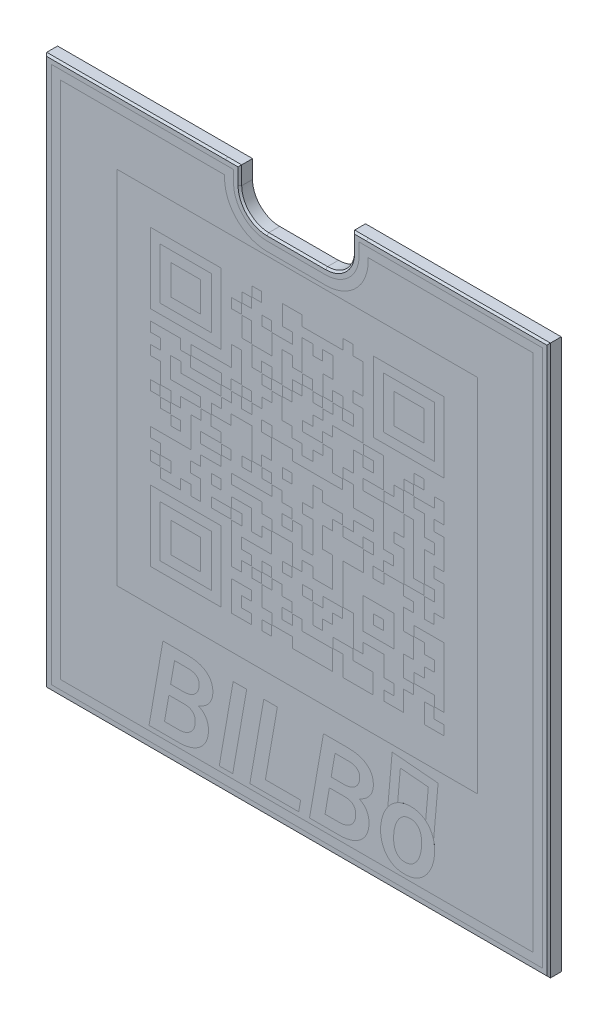
SolidWorks part; units mm, degrees
ref_plane "Front Plane" through (0, 0, 0) normal (0, 0, 1) x (1, 0, 0)
ref_plane "Top Plane" through (0, 0, 0) normal (0, 1, 0) x (1, 0, 0)
ref_plane "Right Plane" through (0, 0, 0) normal (1, 0, 0) x (0, 0, -1)
sketch "Sketch1" plane through (0, 0, 0) normal (0, 0, 1) x (1, 0, 0)
  line L0 (48, -68) -> (-48, -68) construction
  line L1 (56, -32.5) -> (56, -60) construction
  line L2 (56, 46) -> (56, -24.5) construction
  line L3 (-56, -24.5) -> (-56, 46) construction
  line L5 (-15, 54.4) -> (-15, 29) construction
  line L6 (-15, 29) -> (15, 29) construction
  line L7 (15, 29) -> (15, 54) construction
  line L8 (48, 54) -> (15, 54) construction
  line L9 (48, -68) -> (-48, -68) construction
  line L10 (56, -32.5) -> (56, -60) construction
  line L11 (56, 46) -> (56, -24.5) construction
  line L12 (-56, -24.5) -> (-56, 46) construction
  line L13 (-15, 54.4) -> (-48, 54.4) construction
  line L14 (-15, 54.4) -> (-15, 29) construction
  line L15 (-15, 29) -> (15, 29) construction
  line L16 (15, 29) -> (15, 54) construction
  line L17 (48, 54) -> (15, 54) construction
  line L18 (-15.25, 54.05) -> (-15.25, 28.75)
  line L19 (-55.65, 54.05) -> (-15.25, 54.05)
  line L20 (-55.65, 54.05) -> (-55.65, -67.65)
  line L21 (-55.65, -67.65) -> (55.825, -67.65)
  line L22 (55.825, 54.05) -> (55.825, -67.65)
  line L23 (-15.25, 28.75) -> (15.125, 28.75)
  line L24 (15.125, 28.75) -> (15.125, 54.05)
  line L25 (15.125, 54.05) -> (55.825, 54.05)
  circle A0 centre (-52, -64) radius 2.1 construction
  circle A3 centre (52, 50) radius 2.1 construction
  circle A4 centre (-52, 50) radius 2.1 construction
  circle A5 centre (-52, -64) radius 2.1 construction
  circle A6 centre (-52, 2.9) radius 2.15 construction
  circle A7 centre (52, 2.9) radius 2.15 construction
  circle A8 centre (52, 50) radius 2.1 construction
  circle A9 centre (-52, 50) radius 2.1 construction
  circle A10 centre (-52, 50) radius 1.35
  circle A11 centre (-52, 2.9) radius 1.35
  circle A12 centre (-52, -64) radius 1.35
  circle A13 centre (52, 50) radius 1.35
  circle A14 centre (52, 2.9) radius 1.35
  circle A15 centre (52, -64) radius 1.35
  circle A16 centre (-52, 2.9) radius 2.15 construction
  circle A17 centre (52, 2.9) radius 2.15 construction
  dimension "D5" = 2.7
  dimension "D1" = 0.35
  dimension "D2" = 0.35
  dimension "D3" = 0.35
  dimension "D4" = 0.35
  dimension "D6" = 0.25
  dimension "D7" = 0.25
  dimension "D8" = 0.25
extrude "Boss-Extrude1" add sketch "Sketch1" along normal blind 2.8
sketch "Sketch2" plane through (0, 0, 2.8) normal (0, 0, 1) x (1, 0, 0)
  line L5 (15.125, 28.75) -> (-15.25, 28.75) construction
  line L8 (-45.5, -63.25) -> (45.5, -63.25)
  line L9 (-45.5, -63.25) -> (-45.5, 27.75)
  line L10 (-45.5, 27.75) -> (45.5, 27.75)
  line L11 (45.5, -63.25) -> (45.5, 27.75)
  line L31 (-42, 24.25) -> (-28, 24.25)
  line L32 (-42, 24.25) -> (-42, 10.25)
  line L33 (-42, 10.25) -> (-28, 10.25)
  line L34 (-28, 24.25) -> (-28, 10.25)
  line L35 (-28, 24.25) -> (-14, 24.25)
  line L36 (-28, 24.25) -> (-28, 10.25)
  line L37 (-28, 10.25) -> (-14, 10.25)
  line L38 (-14, 24.25) -> (-14, 10.25)
  line L39 (-14, 24.25) -> (0, 24.25)
  line L40 (-14, 24.25) -> (-14, 10.25)
  line L41 (-14, 10.25) -> (0, 10.25)
  line L42 (0, 24.25) -> (0, 10.25)
  line L43 (0, 24.25) -> (14, 24.25)
  line L44 (0, 24.25) -> (0, 10.25)
  line L45 (0, 10.25) -> (14, 10.25)
  line L46 (14, 24.25) -> (14, 10.25)
  line L47 (14, 24.25) -> (28, 24.25)
  line L48 (14, 24.25) -> (14, 10.25)
  line L49 (14, 10.25) -> (28, 10.25)
  line L50 (28, 24.25) -> (28, 10.25)
  line L51 (28, 24.25) -> (42, 24.25)
  line L52 (28, 24.25) -> (28, 10.25)
  line L53 (28, 10.25) -> (42, 10.25)
  line L54 (42, 24.25) -> (42, 10.25)
  line L55 (-42, 10.25) -> (-28, 10.25)
  line L56 (-42, 10.25) -> (-42, -3.75)
  line L57 (-42, -3.75) -> (-28, -3.75)
  line L58 (-28, 10.25) -> (-28, -3.75)
  line L59 (-28, -3.75) -> (-14, -3.75)
  line L60 (-28, -3.75) -> (-28, 10.25)
  line L61 (-28, 10.25) -> (-14, 10.25)
  line L62 (-14, -3.75) -> (-14, 10.25)
  line L63 (-14, -3.75) -> (0, -3.75)
  line L64 (-14, -3.75) -> (-14, 10.25)
  line L65 (-14, 10.25) -> (0, 10.25)
  line L66 (0, -3.75) -> (0, 10.25)
  line L67 (0, -3.75) -> (14, -3.75)
  line L68 (0, -3.75) -> (0, 10.25)
  line L69 (0, 10.25) -> (14, 10.25)
  line L70 (14, -3.75) -> (14, 10.25)
  line L71 (14, -3.75) -> (28, -3.75)
  line L72 (14, -3.75) -> (14, 10.25)
  line L73 (14, 10.25) -> (28, 10.25)
  line L74 (28, -3.75) -> (28, 10.25)
  line L75 (28, -3.75) -> (42, -3.75)
  line L76 (28, -3.75) -> (28, 10.25)
  line L77 (28, 10.25) -> (42, 10.25)
  line L78 (42, -3.75) -> (42, 10.25)
  line L79 (42, -3.75) -> (28, -3.75)
  line L80 (42, -3.75) -> (42, -17.75)
  line L81 (42, -17.75) -> (28, -17.75)
  line L82 (28, -3.75) -> (28, -17.75)
  line L83 (14, -3.75) -> (28, -3.75)
  line L84 (14, -3.75) -> (14, -17.75)
  line L85 (14, -17.75) -> (28, -17.75)
  line L86 (28, -3.75) -> (28, -17.75)
  line L87 (0, -3.75) -> (14, -3.75)
  line L88 (0, -3.75) -> (0, -17.75)
  line L89 (0, -17.75) -> (14, -17.75)
  line L90 (14, -3.75) -> (14, -17.75)
  line L91 (-14, -3.75) -> (0, -3.75)
  line L92 (-14, -3.75) -> (-14, -17.75)
  line L93 (-14, -17.75) -> (0, -17.75)
  line L94 (0, -3.75) -> (0, -17.75)
  line L95 (-28, -3.75) -> (-14, -3.75)
  line L96 (-28, -3.75) -> (-28, -17.75)
  line L97 (-28, -17.75) -> (-14, -17.75)
  line L98 (-14, -3.75) -> (-14, -17.75)
  line L99 (-42, -3.75) -> (-28, -3.75)
  line L100 (-42, -3.75) -> (-42, -17.75)
  line L101 (-42, -17.75) -> (-28, -17.75)
  line L102 (-28, -3.75) -> (-28, -17.75)
  line L103 (-42, -17.75) -> (-28, -17.75)
  line L104 (-42, -17.75) -> (-42, -31.75)
  line L105 (-42, -31.75) -> (-28, -31.75)
  line L106 (-28, -17.75) -> (-28, -31.75)
  line L107 (-28, -31.75) -> (-14, -31.75)
  line L108 (-28, -31.75) -> (-28, -17.75)
  line L109 (-28, -17.75) -> (-14, -17.75)
  line L110 (-14, -31.75) -> (-14, -17.75)
  line L111 (-14, -17.75) -> (0, -17.75)
  line L112 (-14, -17.75) -> (-14, -31.75)
  line L113 (-14, -31.75) -> (0, -31.75)
  line L114 (0, -17.75) -> (0, -31.75)
  line L115 (0, -31.75) -> (14, -31.75)
  line L116 (0, -31.75) -> (0, -17.75)
  line L117 (0, -17.75) -> (14, -17.75)
  line L118 (14, -31.75) -> (14, -17.75)
  line L119 (14, -31.75) -> (28, -31.75)
  line L120 (14, -31.75) -> (14, -17.75)
  line L121 (14, -17.75) -> (28, -17.75)
  line L122 (28, -31.75) -> (28, -17.75)
  line L123 (28, -31.75) -> (42, -31.75)
  line L124 (28, -31.75) -> (28, -17.75)
  line L125 (28, -17.75) -> (42, -17.75)
  line L126 (42, -31.75) -> (42, -17.75)
  line L127 (-42, -31.75) -> (-28, -31.75)
  line L128 (-42, -31.75) -> (-42, -45.75)
  line L129 (-42, -45.75) -> (-28, -45.75)
  line L130 (-28, -31.75) -> (-28, -45.75)
  line L131 (-28, -45.75) -> (-14, -45.75)
  line L132 (-28, -45.75) -> (-28, -31.75)
  line L133 (-28, -31.75) -> (-14, -31.75)
  line L134 (-14, -45.75) -> (-14, -31.75)
  line L135 (-14, -45.75) -> (0, -45.75)
  line L136 (-14, -45.75) -> (-14, -31.75)
  line L137 (-14, -31.75) -> (0, -31.75)
  line L138 (0, -45.75) -> (0, -31.75)
  line L139 (0, -45.75) -> (14, -45.75)
  line L140 (0, -45.75) -> (0, -31.75)
  line L141 (0, -31.75) -> (14, -31.75)
  line L142 (14, -45.75) -> (14, -31.75)
  line L143 (14, -45.75) -> (28, -45.75)
  line L144 (14, -45.75) -> (14, -31.75)
  line L145 (14, -31.75) -> (28, -31.75)
  line L146 (28, -45.75) -> (28, -31.75)
  line L147 (28, -45.75) -> (42, -45.75)
  line L148 (28, -45.75) -> (28, -31.75)
  line L149 (28, -31.75) -> (42, -31.75)
  line L150 (42, -45.75) -> (42, -31.75)
  line L151 (42, -45.75) -> (28, -45.75)
  line L152 (42, -45.75) -> (42, -59.75)
  line L153 (42, -59.75) -> (28, -59.75)
  line L154 (28, -45.75) -> (28, -59.75)
  line L155 (28, -59.75) -> (14, -59.75)
  line L156 (28, -59.75) -> (28, -45.75)
  line L157 (28, -45.75) -> (14, -45.75)
  line L158 (14, -59.75) -> (14, -45.75)
  line L159 (0, -45.75) -> (14, -45.75)
  line L160 (0, -45.75) -> (0, -59.75)
  line L161 (0, -59.75) -> (14, -59.75)
  line L162 (14, -45.75) -> (14, -59.75)
  line L163 (-14, -45.75) -> (0, -45.75)
  line L164 (-14, -45.75) -> (-14, -59.75)
  line L165 (-14, -59.75) -> (0, -59.75)
  line L166 (0, -45.75) -> (0, -59.75)
  line L167 (-28, -45.75) -> (-14, -45.75)
  line L168 (-28, -45.75) -> (-28, -59.75)
  line L169 (-28, -59.75) -> (-14, -59.75)
  line L170 (-14, -45.75) -> (-14, -59.75)
  line L171 (-42, -45.75) -> (-28, -45.75)
  line L172 (-42, -45.75) -> (-42, -59.75)
  line L173 (-42, -59.75) -> (-28, -59.75)
  line L174 (-28, -45.75) -> (-28, -59.75)
  point P3 (0, 27.75)
  point P58 (-45.5, -17.75)
  dimension "D1" = 1
  dimension "D2" = 91
  dimension "D3" = 14
sketch "Sketch3" plane through (0, 0, 2.8) normal (0, 0, 1) x (1, 0, 0)
  circle A0 centre (-52, 50) radius 2.5
  circle A1 centre (-52, 2.9) radius 2.5
  circle A2 centre (-52, -64) radius 2.5
  circle A3 centre (52, -64) radius 2.5
  circle A4 centre (52, 2.9) radius 2.5
  circle A5 centre (52, 50) radius 2.5
  dimension "D1" = 5
extrude "Cut-Extrude1" cut sketch "Sketch3" against normal blind 2.2
sketch "Sketch4" plane through (0, 0, 0) normal (0, 0, -1) x (-1, 0, 0)
  line L0 (-15.125, 28.75) -> (15.25, 28.75) construction
  line L1 (-45.65, -57.65) -> (45.65, -57.65)
  line L2 (-45.65, -57.65) -> (-45.65, 27.75)
  line L3 (-45.65, 27.75) -> (45.65, 27.75)
  line L4 (45.65, -57.65) -> (45.65, 27.75)
  line L5 (-45.65, -57.65) -> (45.65, 27.75) construction
  line L6 (-45.65, 27.75) -> (45.65, -57.65) construction
  line L7 (55.65, 54.05) -> (55.65, -67.65) construction
  line L8 (55.65, -67.65) -> (-55.825, -67.65) construction
  point P0 (0, -14.95)
  point P9 (0, 27.75)
  dimension "D1" = 1
  dimension "D2" = 10
  dimension "D3" = 10
extrude "Cut-Extrude2" cut sketch "Sketch4" against normal blind 1.5
sketch "Sketch5" plane through (0, 0, 0.6) normal (0, 0, 1) x (1, 0, 0)
  line L2 (-53.35, 47.8958) -> (-53.35, 52.1042)
  line L4 (-50.65, 47.8958) -> (-50.65, 52.1042)
  line L5 (-53.35, 47.8958) -> (-50.65, 52.1042) construction
  line L6 (-53.35, 52.1042) -> (-50.65, 47.8958) construction
  line L8 (-53.35, 0.7958) -> (-53.35, 5.0042)
  line L10 (-50.65, 0.7958) -> (-50.65, 5.0042)
  line L11 (-53.35, 0.7958) -> (-50.65, 5.0042) construction
  line L12 (-53.35, 5.0042) -> (-50.65, 0.7958) construction
  line L14 (-53.35, -66.1042) -> (-53.35, -61.8958)
  line L16 (-50.65, -66.1042) -> (-50.65, -61.8958)
  line L17 (-53.35, -66.1042) -> (-50.65, -61.8958) construction
  line L18 (-53.35, -61.8958) -> (-50.65, -66.1042) construction
  circle A0 centre (-52, 50) radius 2.5 construction
  circle A1 centre (-52, 50) radius 1.35 construction
  arc A2 (-50.65, 52.1042) -> (-53.35, 52.1042) centre (-52, 50) ccw
  arc A3 (-53.35, 47.8958) -> (-50.65, 47.8958) centre (-52, 50) ccw
  circle A4 centre (-52, 2.9) radius 2.5 construction
  circle A5 centre (-52, 2.9) radius 1.35 construction
  circle A6 centre (-52, 2.9) radius 2.5 construction
  arc A7 (-50.65, 5.0042) -> (-53.35, 5.0042) centre (-52, 2.9) ccw
  arc A8 (-53.35, 0.7958) -> (-50.65, 0.7958) centre (-52, 2.9) ccw
  circle A9 centre (-52, -64) radius 2.5 construction
  circle A10 centre (-52, -64) radius 1.35 construction
  circle A11 centre (-52, -64) radius 2.5 construction
  arc A12 (-50.65, -61.8958) -> (-53.35, -61.8958) centre (-52, -64) ccw
  arc A13 (-53.35, -66.1042) -> (-50.65, -66.1042) centre (-52, -64) ccw
  point P0 (-52, 50)
  point P10 (-52, 2.9)
  point P22 (-52, -64)
extrude "Cut-Extrude3" cut sketch "Sketch5" against normal blind 0.2
sketch "Sketch6" plane through (0, 0, 0.4) normal (0, 0, 1) x (1, 0, 0)
  line L0 (-50.65, -66.1042) -> (-50.65, -61.8958) construction
  line L1 (-53.35, -65.35) -> (-50.65, -65.35)
  line L2 (-53.35, -65.35) -> (-53.35, -62.65)
  line L3 (-53.35, -62.65) -> (-50.65, -62.65)
  line L4 (-50.65, -65.35) -> (-50.65, -62.65)
  line L5 (-53.35, -65.35) -> (-50.65, -62.65) construction
  line L6 (-53.35, -62.65) -> (-50.65, -65.35) construction
  line L7 (-50.65, 0.7958) -> (-50.65, 5.0042) construction
  line L8 (-53.35, 1.55) -> (-50.65, 1.55)
  line L9 (-53.35, 1.55) -> (-53.35, 4.25)
  line L10 (-53.35, 4.25) -> (-50.65, 4.25)
  line L11 (-50.65, 1.55) -> (-50.65, 4.25)
  line L12 (-53.35, 1.55) -> (-50.65, 4.25) construction
  line L13 (-53.35, 4.25) -> (-50.65, 1.55) construction
  line L14 (-50.65, 47.8958) -> (-50.65, 52.1042) construction
  line L15 (-53.35, 48.65) -> (-50.65, 48.65)
  line L16 (-53.35, 48.65) -> (-53.35, 51.35)
  line L17 (-53.35, 51.35) -> (-50.65, 51.35)
  line L18 (-50.65, 48.65) -> (-50.65, 51.35)
  line L19 (-53.35, 48.65) -> (-50.65, 51.35) construction
  line L20 (-53.35, 51.35) -> (-50.65, 48.65) construction
  arc A0 (-50.65, -64) -> (-53.35, -64) centre (-52, -64) ccw construction
  arc A1 (-50.65, 2.9) -> (-53.35, 2.9) centre (-52, 2.9) ccw construction
  arc A2 (-50.65, 50) -> (-53.35, 50) centre (-52, 50) ccw construction
  point P0 (-52, -64)
  point P11 (-52, 2.9)
  point P22 (-52, 50)
extrude "Cut-Extrude4" cut sketch "Sketch6" against normal blind 0.2
mirror "Mirror1" about plane through (0, 0, 0) normal (1, 0, 0) of "Cut-Extrude4", "Cut-Extrude3"
chamfer "Chamfer1" distance 0.4 angle 45 8 edges at (0.0875, -67.65, 2.8) (55.825, -6.8, 2.8) (35.475, 54.05, 2.8) (15.125, 41.4, 2.8) (-0.0625, 28.75, 2.8) (-15.25, 41.4, 2.8) (-35.45, 54.05, 2.8) (-55.65, -6.8, 2.8)
sketch "Sketch11" plane through (0, 0, 2.8) normal (0, 0, 1) x (1, 0, 0)
  line L0 (15.125, 54.05) -> (55.825, 54.05) construction
  line L1 (-15.65, 28.35) -> (15.525, 28.35)
  line L2 (-15.65, 28.35) -> (-15.65, 54.05)
  line L3 (-15.65, 54.05) -> (15.525, 54.05)
  line L4 (15.525, 28.35) -> (15.525, 54.05)
  line L5 (15.525, 53.65) -> (15.525, 28.35) construction
extrude "Boss-Extrude4" add sketch "Sketch11" against normal up to surface (2.8 mm away) up to face at (0, -14.95, 0)
chamfer "Chamfer2" distance 0.4 angle 45 1 edges at (-0.0625, 54.05, 2.8)
sketch "Sketch12" plane through (0, 0, 2.8) normal (0, 0, 1) x (1, 0, 0)
  circle A0 centre (52, -64) radius 2.5 construction
  circle A1 centre (52, 50) radius 2.5 construction
  circle A2 centre (52, 2.9) radius 2.5 construction
  circle A3 centre (-52, -64) radius 2.5 construction
  circle A4 centre (-52, 2.9) radius 2.5 construction
  circle A5 centre (-52, 50) radius 2.5 construction
  circle A6 centre (52, -64) radius 2.5
  circle A7 centre (52, 50) radius 2.5
  circle A8 centre (52, 2.9) radius 2.5
  circle A9 centre (-52, -64) radius 2.5
  circle A10 centre (-52, 2.9) radius 2.5
  circle A11 centre (-52, 50) radius 2.5
extrude "Boss-Extrude5" add sketch "Sketch12" against normal up to surface (2.8 mm away) up to face at (0.0875, -6.8, 0)
sketch "Sketch13" plane through (0, 0, 0) normal (0, 0, -1) x (-1, 0, 0)
  line L0 (-55.825, -67.65) -> (-55.825, 54.05) construction
  line L1 (-50.825, 49.05) -> (50.825, 49.05) construction
  line L2 (-50.825, 49.05) -> (-50.825, -62.65) construction
  line L3 (-50.825, -62.65) -> (50.825, -62.65) construction
  line L4 (50.825, 49.05) -> (50.825, -62.65) construction
  line L5 (-55.825, 54.05) -> (55.65, 54.05) construction
  line L6 (55.65, -67.65) -> (-55.825, -67.65) construction
  circle A0 centre (-50.825, 49.05) radius 3.2
  circle A1 centre (50.825, 49.05) radius 3.2
  circle A2 centre (50.825, -62.65) radius 3.2
  circle A3 centre (-50.825, -62.65) radius 3.2
  circle A4 centre (-50.825, -6.8) radius 3.2
  circle A5 centre (50.825, -6.8) radius 3.2
  point P4 (0, 49.05)
  dimension "D1" = 6.4
  dimension "D2" = 5
  dimension "D3" = 5
  dimension "D4" = 5
extrude "Cut-Extrude7" cut sketch "Sketch13" against normal blind 1.2
sketch "Sketch14" plane through (0, 0, 2.8) normal (0, 0, 1) x (1, 0, 0)
  line L0 (-55.65, 54.05) -> (-15.65, 54.05) construction
  line L1 (-12.5, 54.05) -> (12.5, 54.05)
  line L2 (-12.5, 54.05) -> (-12.5, 44.05)
  line L3 (-12.5, 44.05) -> (12.5, 44.05)
  line L4 (12.5, 54.05) -> (12.5, 44.05)
  point P6 (0, 44.05)
  dimension "D1" = 25
  dimension "D2" = 10
extrude "Cut-Extrude8" cut sketch "Sketch14" against normal through all
fillet "Fillet1" radius 6 2 edges at (12.5, 44.05, 1.4) (-12.5, 44.05, 1.4)
chamfer "Chamfer3" distance 0.4 angle 45 5 edges at (-12.5, 51.85, 2.8) (12.5, 51.85, 2.8) (-10.7426, 45.8074, 2.8) (10.7426, 45.8074, 2.8) (0, 44.05, 2.8)
sketch "Sketch22" plane through (0, 0, 2.8) normal (0, 0, 1) x (1, 0, 0)
  line L0 (-39.7032, 39.7992) -> (40.1257, 39.7992)
  line L1 (40.1257, 39.7992) -> (40.1257, -40.0298)
  line L2 (40.1257, -40.0298) -> (-39.7032, -40.0298)
  line L3 (-39.7032, -40.0298) -> (-39.7032, 39.7992)
  line L4 (-32.2887, 30.1954) -> (-32.2887, 16.7799)
  line L5 (-32.2887, 16.7799) -> (-16.6839, 16.7799)
  line L6 (-16.6839, 16.7799) -> (-16.6839, 32.3847)
  line L7 (-16.6839, 32.3847) -> (-32.2887, 32.3847)
  line L8 (-32.2887, 32.3847) -> (-32.2887, 30.1954)
  line L9 (-9.8364, 30.2513) -> (-7.703, 30.2513)
  line L10 (-7.703, 30.2513) -> (-7.703, 32.3847)
  line L11 (-7.703, 32.3847) -> (-9.8364, 32.3847)
  line L12 (-9.8364, 32.3847) -> (-9.8364, 30.2513)
  line L13 (-3.1007, 30.1954) -> (-3.1007, 28.006)
  line L14 (-3.1007, 28.006) -> (-0.8554, 28.006)
  line L15 (-0.8554, 28.006) -> (-0.8554, 25.649)
  line L16 (-0.8554, 25.649) -> (-5.3459, 25.649)
  line L17 (-5.3459, 25.649) -> (-5.3459, 21.1585)
  line L18 (-5.3459, 21.1585) -> (-9.8364, 21.1585)
  line L19 (-9.8364, 21.1585) -> (-9.8364, 16.7799)
  line L20 (-9.8364, 16.7799) -> (-7.703, 16.7799)
  line L21 (-7.703, 16.7799) -> (-7.703, 19.0251)
  line L22 (-7.703, 19.0251) -> (-5.3459, 19.0251)
  line L23 (-5.3459, 19.0251) -> (-5.3459, 16.7799)
  line L24 (-5.3459, 16.7799) -> (-3.2125, 16.7799)
  line L25 (-3.2125, 16.7799) -> (-3.2125, 23.5156)
  line L26 (-3.2125, 23.5156) -> (-0.8554, 23.5156)
  line L27 (-0.8554, 23.5156) -> (-0.8554, 21.2703)
  line L28 (-0.8554, 21.2703) -> (1.278, 21.2703)
  line L29 (1.278, 21.2703) -> (1.278, 28.006)
  line L30 (1.278, 28.006) -> (3.635, 28.006)
  line L31 (3.635, 28.006) -> (3.635, 25.7608)
  line L32 (3.635, 25.7608) -> (5.7684, 25.7608)
  line L33 (5.7684, 25.7608) -> (5.7684, 28.006)
  line L34 (5.7684, 28.006) -> (8.1255, 28.006)
  line L35 (8.1255, 28.006) -> (8.1255, 23.4037)
  line L36 (8.1255, 23.4037) -> (5.8803, 23.4037)
  line L37 (5.8803, 23.4037) -> (5.8803, 19.0251)
  line L38 (5.8803, 19.0251) -> (8.0137, 19.0251)
  line L39 (8.0137, 19.0251) -> (8.0137, 21.2703)
  line L40 (8.0137, 21.2703) -> (10.3707, 21.2703)
  line L41 (10.3707, 21.2703) -> (10.3707, 19.0251)
  line L42 (10.3707, 19.0251) -> (12.616, 19.0251)
  line L43 (12.616, 19.0251) -> (12.616, 16.668)
  line L44 (12.616, 16.668) -> (10.2589, 16.668)
  line L45 (10.2589, 16.668) -> (10.2589, 18.9133)
  line L46 (10.2589, 18.9133) -> (8.1255, 18.9133)
  line L47 (8.1255, 18.9133) -> (8.1255, 16.668)
  line L48 (8.1255, 16.668) -> (5.8803, 16.668)
  line L49 (5.8803, 16.668) -> (5.8803, 14.4228)
  line L50 (5.8803, 14.4228) -> (3.635, 14.4228)
  line L51 (3.635, 14.4228) -> (3.635, 12.1776)
  line L52 (3.635, 12.1776) -> (1.3898, 12.1776)
  line L53 (1.3898, 12.1776) -> (1.3898, 10.0442)
  line L54 (1.3898, 10.0442) -> (5.7684, 10.0442)
  line L55 (5.7684, 10.0442) -> (5.7684, 12.2894)
  line L56 (5.7684, 12.2894) -> (8.0137, 12.2894)
  line L57 (8.0137, 12.2894) -> (8.0137, 14.5346)
  line L58 (8.0137, 14.5346) -> (14.7494, 14.5346)
  line L59 (14.7494, 14.5346) -> (14.7494, 21.1585)
  line L60 (14.7494, 21.1585) -> (12.5041, 21.1585)
  line L61 (12.5041, 21.1585) -> (12.5041, 23.5156)
  line L62 (12.5041, 23.5156) -> (14.7494, 23.5156)
  line L63 (14.7494, 23.5156) -> (14.7494, 30.1394)
  line L64 (14.7494, 30.1394) -> (12.5041, 30.1394)
  line L65 (12.5041, 30.1394) -> (12.5041, 32.3847)
  line L66 (12.5041, 32.3847) -> (10.3707, 32.3847)
  line L67 (10.3707, 32.3847) -> (10.3707, 30.1394)
  line L68 (10.3707, 30.1394) -> (1.278, 30.1394)
  line L69 (1.278, 30.1394) -> (1.278, 32.3847)
  line L70 (1.278, 32.3847) -> (-3.1007, 32.3847)
  line L71 (-3.1007, 32.3847) -> (-3.1007, 30.1954)
  line L72 (17.1064, 30.1954) -> (17.1064, 16.7799)
  line L73 (17.1064, 16.7799) -> (32.7113, 16.7799)
  line L74 (32.7113, 16.7799) -> (32.7113, 32.3847)
  line L75 (32.7113, 32.3847) -> (17.1064, 32.3847)
  line L76 (17.1064, 32.3847) -> (17.1064, 30.1954)
  line L77 (-30.0994, 30.2513) -> (-18.8173, 30.2513)
  line L78 (-18.8173, 30.2513) -> (-18.8173, 18.9133)
  line L79 (-18.8173, 18.9133) -> (-30.1553, 18.9133)
  line L80 (-30.1553, 18.9133) -> (-30.1553, 30.2513)
  line L81 (-30.1553, 30.2513) -> (-30.1273, 30.2513)
  line L82 (-30.1273, 30.2513) -> (-30.0994, 30.2513)
  line L83 (19.2958, 30.2513) -> (30.5778, 30.2513)
  line L84 (30.5778, 30.2513) -> (30.5778, 18.9133)
  line L85 (30.5778, 18.9133) -> (19.2398, 18.9133)
  line L86 (19.2398, 18.9133) -> (19.2398, 30.2513)
  line L87 (19.2398, 30.2513) -> (19.2679, 30.2513)
  line L88 (19.2679, 30.2513) -> (19.2958, 30.2513)
  line L89 (-12.0816, 28.006) -> (-9.9482, 28.006)
  line L90 (-9.9482, 28.006) -> (-9.9482, 30.1394)
  line L91 (-9.9482, 30.1394) -> (-12.0816, 30.1394)
  line L92 (-12.0816, 30.1394) -> (-12.0816, 28.006)
  line L93 (-27.7983, 25.7049) -> (-27.7983, 21.2703)
  line L94 (-27.7983, 21.2703) -> (-21.1744, 21.2703)
  line L95 (-21.1744, 21.2703) -> (-21.1744, 27.8942)
  line L96 (-21.1744, 27.8942) -> (-27.7983, 27.8942)
  line L97 (-27.7983, 27.8942) -> (-27.7983, 25.7049)
  line L98 (-14.3269, 25.7608) -> (-12.1934, 25.7608)
  line L99 (-12.1934, 25.7608) -> (-12.1934, 27.8942)
  line L100 (-12.1934, 27.8942) -> (-14.3269, 27.8942)
  line L101 (-14.3269, 27.8942) -> (-14.3269, 25.7608)
  line L102 (-7.5912, 25.7608) -> (-5.4577, 25.7608)
  line L103 (-5.4577, 25.7608) -> (-5.4577, 27.8942)
  line L104 (-5.4577, 27.8942) -> (-7.5912, 27.8942)
  line L105 (-7.5912, 27.8942) -> (-7.5912, 25.7608)
  line L106 (21.5969, 25.7049) -> (21.5969, 21.2703)
  line L107 (21.5969, 21.2703) -> (28.2208, 21.2703)
  line L108 (28.2208, 21.2703) -> (28.2208, 27.8942)
  line L109 (28.2208, 27.8942) -> (21.5969, 27.8942)
  line L110 (21.5969, 27.8942) -> (21.5969, 25.7049)
  line L111 (-12.0816, 23.4597) -> (-12.0816, 21.2703)
  line L112 (-12.0816, 21.2703) -> (-9.9482, 21.2703)
  line L113 (-9.9482, 21.2703) -> (-9.9482, 25.649)
  line L114 (-9.9482, 25.649) -> (-12.0816, 25.649)
  line L115 (-12.0816, 25.649) -> (-12.0816, 23.4597)
  line L116 (1.3898, 19.0251) -> (3.5232, 19.0251)
  line L117 (3.5232, 19.0251) -> (3.5232, 21.1585)
  line L118 (3.5232, 21.1585) -> (1.3898, 21.1585)
  line L119 (1.3898, 21.1585) -> (1.3898, 19.0251)
  line L120 (-14.3269, 16.7239) -> (-14.3269, 14.4228)
  line L121 (-14.3269, 14.4228) -> (-23.3078, 14.4228)
  line L122 (-23.3078, 14.4228) -> (-23.3078, 12.2894)
  line L123 (-23.3078, 12.2894) -> (-16.5721, 12.2894)
  line L124 (-16.5721, 12.2894) -> (-16.5721, 10.0442)
  line L125 (-16.5721, 10.0442) -> (-14.4387, 10.0442)
  line L126 (-14.4387, 10.0442) -> (-14.4387, 12.2894)
  line L127 (-14.4387, 12.2894) -> (-12.1934, 12.2894)
  line L128 (-12.1934, 12.2894) -> (-12.1934, 18.9133)
  line L129 (-12.1934, 18.9133) -> (-14.3269, 18.9133)
  line L130 (-14.3269, 18.9133) -> (-14.3269, 16.7239)
  line L131 (-0.8554, 16.7799) -> (1.278, 16.7799)
  line L132 (1.278, 16.7799) -> (1.278, 18.9133)
  line L133 (1.278, 18.9133) -> (-0.8554, 18.9133)
  line L134 (-0.8554, 18.9133) -> (-0.8554, 16.7799)
  line L135 (3.635, 16.7799) -> (5.7684, 16.7799)
  line L136 (5.7684, 16.7799) -> (5.7684, 18.9133)
  line L137 (5.7684, 18.9133) -> (3.635, 18.9133)
  line L138 (3.635, 18.9133) -> (3.635, 16.7799)
  line L139 (-7.5912, 14.5346) -> (-5.4577, 14.5346)
  line L140 (-5.4577, 14.5346) -> (-5.4577, 16.668)
  line L141 (-5.4577, 16.668) -> (-7.5912, 16.668)
  line L142 (-7.5912, 16.668) -> (-7.5912, 14.5346)
  line L143 (-3.1007, 14.5346) -> (-0.9673, 14.5346)
  line L144 (-0.9673, 14.5346) -> (-0.9673, 16.668)
  line L145 (-0.9673, 16.668) -> (-3.1007, 16.668)
  line L146 (-3.1007, 16.668) -> (-3.1007, 14.5346)
  line L147 (-32.2887, 12.2894) -> (-30.0435, 12.2894)
  line L148 (-30.0435, 12.2894) -> (-30.0435, 9.9323)
  line L149 (-30.0435, 9.9323) -> (-32.2887, 9.9323)
  line L150 (-32.2887, 9.9323) -> (-32.2887, 7.7989)
  line L151 (-32.2887, 7.7989) -> (-30.0435, 7.7989)
  line L152 (-30.0435, 7.7989) -> (-30.0435, 3.3085)
  line L153 (-30.0435, 3.3085) -> (-27.7983, 3.3085)
  line L154 (-27.7983, 3.3085) -> (-27.7983, 1.0632)
  line L155 (-27.7983, 1.0632) -> (-25.6649, 1.0632)
  line L156 (-25.6649, 1.0632) -> (-25.6649, 3.3085)
  line L157 (-25.6649, 3.3085) -> (-21.1744, 3.3085)
  line L158 (-21.1744, 3.3085) -> (-21.1744, 5.4419)
  line L159 (-21.1744, 5.4419) -> (-27.9101, 5.4419)
  line L160 (-27.9101, 5.4419) -> (-27.9101, 10.0442)
  line L161 (-27.9101, 10.0442) -> (-25.553, 10.0442)
  line L162 (-25.553, 10.0442) -> (-25.553, 7.7989)
  line L163 (-25.553, 7.7989) -> (-16.6839, 7.7989)
  line L164 (-16.6839, 7.7989) -> (-16.6839, 9.9323)
  line L165 (-16.6839, 9.9323) -> (-23.4196, 9.9323)
  line L166 (-23.4196, 9.9323) -> (-23.4196, 12.1776)
  line L167 (-23.4196, 12.1776) -> (-25.6649, 12.1776)
  line L168 (-25.6649, 12.1776) -> (-25.6649, 14.4228)
  line L169 (-25.6649, 14.4228) -> (-32.2887, 14.4228)
  line L170 (-32.2887, 14.4228) -> (-32.2887, 12.2894)
  line L171 (-5.8228, 12.1776) -> (-7.5912, 12.1776)
  line L172 (-7.5912, 12.1776) -> (-7.5912, 9.9323)
  line L173 (-7.5912, 9.9323) -> (-9.8364, 9.9323)
  line L174 (-9.8364, 9.9323) -> (-9.8364, 7.6871)
  line L175 (-9.8364, 7.6871) -> (-12.1934, 7.6871)
  line L176 (-12.1934, 7.6871) -> (-12.1934, 9.9323)
  line L177 (-12.1934, 9.9323) -> (-14.3269, 9.9323)
  line L178 (-14.3269, 9.9323) -> (-14.3269, 7.6871)
  line L179 (-14.3269, 7.6871) -> (-16.5721, 7.6871)
  line L180 (-16.5721, 7.6871) -> (-16.5721, 5.4419)
  line L181 (-16.5721, 5.4419) -> (-18.8173, 5.4419)
  line L182 (-18.8173, 5.4419) -> (-18.8173, 3.3084)
  line L183 (-18.8173, 3.3084) -> (-14.4387, 3.3084)
  line L184 (-14.4387, 3.3084) -> (-14.4387, 5.5537)
  line L185 (-14.4387, 5.5537) -> (-9.8364, 5.5537)
  line L186 (-9.8364, 5.5537) -> (-9.8364, -1.182)
  line L187 (-9.8364, -1.182) -> (-7.703, -1.182)
  line L188 (-7.703, -1.182) -> (-7.703, 1.0632)
  line L189 (-7.703, 1.0632) -> (-5.4577, 1.0632)
  line L190 (-5.4577, 1.0632) -> (-5.4577, 5.4419)
  line L191 (-5.4577, 5.4419) -> (-7.703, 5.4419)
  line L192 (-7.703, 5.4419) -> (-7.703, 7.7989)
  line L193 (-7.703, 7.7989) -> (-5.3459, 7.7989)
  line L194 (-5.3459, 7.7989) -> (-5.3459, 5.5537)
  line L195 (-5.3459, 5.5537) -> (-0.8554, 5.5537)
  line L196 (-0.8554, 5.5537) -> (-0.8554, 3.3084)
  line L197 (-0.8554, 3.3084) -> (10.2589, 3.3084)
  line L198 (10.2589, 3.3084) -> (10.2589, 5.4419)
  line L199 (10.2589, 5.4419) -> (8.0137, 5.4419)
  line L200 (8.0137, 5.4419) -> (8.0137, 9.9323)
  line L201 (8.0137, 9.9323) -> (5.8803, 9.9323)
  line L202 (5.8803, 9.9323) -> (5.8803, 7.6871)
  line L203 (5.8803, 7.6871) -> (3.635, 7.6871)
  line L204 (3.635, 7.6871) -> (3.635, 5.4419)
  line L205 (3.635, 5.4419) -> (1.278, 5.4419)
  line L206 (1.278, 5.4419) -> (1.278, 7.6871)
  line L207 (1.278, 7.6871) -> (-0.9673, 7.6871)
  line L208 (-0.9673, 7.6871) -> (-0.9673, 9.9323)
  line L209 (-0.9673, 9.9323) -> (-3.2125, 9.9323)
  line L210 (-3.2125, 9.9323) -> (-3.2125, 14.4228)
  line L211 (-3.2125, 14.4228) -> (-5.3459, 14.4228)
  line L212 (-5.3459, 14.4228) -> (-5.3459, 12.2335)
  line L213 (14.8612, 12.2894) -> (17.1064, 12.2894)
  line L214 (17.1064, 12.2894) -> (17.1064, 9.9323)
  line L215 (17.1064, 9.9323) -> (14.7494, 9.9323)
  line L216 (14.7494, 9.9323) -> (14.7494, 12.1776)
  line L217 (14.7494, 12.1776) -> (12.616, 12.1776)
  line L218 (12.616, 12.1776) -> (12.616, 7.6871)
  line L219 (12.616, 7.6871) -> (10.3707, 7.6871)
  line L220 (10.3707, 7.6871) -> (10.3707, 5.5537)
  line L221 (10.3707, 5.5537) -> (12.616, 5.5537)
  line L222 (12.616, 5.5537) -> (12.616, 1.0632)
  line L223 (12.616, 1.0632) -> (17.1064, 1.0632)
  line L224 (17.1064, 1.0632) -> (17.1064, -1.2938)
  line L225 (17.1064, -1.2938) -> (12.616, -1.2938)
  line L226 (12.616, -1.2938) -> (12.616, -3.5391)
  line L227 (12.616, -3.5391) -> (10.3707, -3.5391)
  line L228 (10.3707, -3.5391) -> (10.3707, -5.6725)
  line L229 (10.3707, -5.6725) -> (14.7494, -5.6725)
  line L230 (14.7494, -5.6725) -> (14.7494, -3.4273)
  line L231 (14.7494, -3.4273) -> (17.1064, -3.4273)
  line L232 (17.1064, -3.4273) -> (17.1064, -5.7843)
  line L233 (17.1064, -5.7843) -> (14.8612, -5.7843)
  line L234 (14.8612, -5.7843) -> (14.8612, -10.2748)
  line L235 (14.8612, -10.2748) -> (10.3707, -10.2748)
  line L236 (10.3707, -10.2748) -> (10.3707, -19.1439)
  line L237 (10.3707, -19.1439) -> (12.616, -19.1439)
  line L238 (12.616, -19.1439) -> (12.616, -25.8796)
  line L239 (12.616, -25.8796) -> (14.7494, -25.8796)
  line L240 (14.7494, -25.8796) -> (14.7494, -23.6344)
  line L241 (14.7494, -23.6344) -> (19.3517, -23.6344)
  line L242 (19.3517, -23.6344) -> (19.3517, -28.1248)
  line L243 (19.3517, -28.1248) -> (21.5969, -28.1248)
  line L244 (21.5969, -28.1248) -> (21.5969, -30.4819)
  line L245 (21.5969, -30.4819) -> (19.3517, -30.4819)
  line L246 (19.3517, -30.4819) -> (19.3517, -32.6153)
  line L247 (19.3517, -32.6153) -> (23.7303, -32.6153)
  line L248 (23.7303, -32.6153) -> (23.7303, -28.1248)
  line L249 (23.7303, -28.1248) -> (25.9756, -28.1248)
  line L250 (25.9756, -28.1248) -> (25.9756, -25.9914)
  line L251 (25.9756, -25.9914) -> (23.7303, -25.9914)
  line L252 (23.7303, -25.9914) -> (23.7303, -21.3891)
  line L253 (23.7303, -21.3891) -> (25.9756, -21.3891)
  line L254 (25.9756, -21.3891) -> (25.9756, -17.0105)
  line L255 (25.9756, -17.0105) -> (23.7303, -17.0105)
  line L256 (23.7303, -17.0105) -> (23.7303, -12.4082)
  line L257 (23.7303, -12.4082) -> (25.9756, -12.4082)
  line L258 (25.9756, -12.4082) -> (25.9756, -10.2748)
  line L259 (25.9756, -10.2748) -> (23.7303, -10.2748)
  line L260 (23.7303, -10.2748) -> (23.7303, -8.0296)
  line L261 (23.7303, -8.0296) -> (19.3517, -8.0296)
  line L262 (19.3517, -8.0296) -> (19.3517, -10.2748)
  line L263 (19.3517, -10.2748) -> (16.9946, -10.2748)
  line L264 (16.9946, -10.2748) -> (16.9946, -7.9177)
  line L265 (16.9946, -7.9177) -> (19.2398, -7.9177)
  line L266 (19.2398, -7.9177) -> (19.2398, -5.6725)
  line L267 (19.2398, -5.6725) -> (21.4851, -5.6725)
  line L268 (21.4851, -5.6725) -> (21.4851, -3.5391)
  line L269 (21.4851, -3.5391) -> (19.2398, -3.5391)
  line L270 (19.2398, -3.5391) -> (19.2398, 5.4419)
  line L271 (19.2398, 5.4419) -> (14.7494, 5.4419)
  line L272 (14.7494, 5.4419) -> (14.7494, 7.7989)
  line L273 (14.7494, 7.7989) -> (19.2398, 7.7989)
  line L274 (19.2398, 7.7989) -> (19.2398, 14.4228)
  line L275 (19.2398, 14.4228) -> (14.8612, 14.4228)
  line L276 (14.8612, 14.4228) -> (14.8612, 12.2894)
  line L277 (26.0874, 12.2894) -> (28.2208, 12.2894)
  line L278 (28.2208, 12.2894) -> (28.2208, 14.4228)
  line L279 (28.2208, 14.4228) -> (26.0874, 14.4228)
  line L280 (26.0874, 14.4228) -> (26.0874, 12.2894)
  line L281 (-12.0816, 10.0442) -> (-9.9482, 10.0442)
  line L282 (-9.9482, 10.0442) -> (-9.9482, 12.1776)
  line L283 (-9.9482, 12.1776) -> (-12.0816, 12.1776)
  line L284 (-12.0816, 12.1776) -> (-12.0816, 10.0442)
  line L285 (23.8421, 10.0442) -> (25.9756, 10.0442)
  line L286 (25.9756, 10.0442) -> (25.9756, 12.1776)
  line L287 (25.9756, 12.1776) -> (23.8421, 12.1776)
  line L288 (23.8421, 12.1776) -> (23.8421, 10.0442)
  line L289 (30.101, 9.9323) -> (26.0874, 9.9323)
  line L290 (26.0874, 9.9323) -> (26.0874, 7.7989)
  line L291 (26.0874, 7.7989) -> (28.3326, 7.7989)
  line L292 (28.3326, 7.7989) -> (28.3326, 3.3085)
  line L293 (28.3326, 3.3085) -> (30.5778, 3.3085)
  line L294 (30.5778, 3.3085) -> (30.5778, 0.9514)
  line L295 (30.5778, 0.9514) -> (28.3326, 0.9514)
  line L296 (28.3326, 0.9514) -> (28.3326, -5.6725)
  line L297 (28.3326, -5.6725) -> (30.5778, -5.6725)
  line L298 (30.5778, -5.6725) -> (30.5778, -8.0295)
  line L299 (30.5778, -8.0295) -> (28.3326, -8.0295)
  line L300 (28.3326, -8.0295) -> (28.3326, -12.4082)
  line L301 (28.3326, -12.4082) -> (30.466, -12.4082)
  line L302 (30.466, -12.4082) -> (30.466, -10.163)
  line L303 (30.466, -10.163) -> (32.7113, -10.163)
  line L304 (32.7113, -10.163) -> (32.7113, -3.5391)
  line L305 (32.7113, -3.5391) -> (30.466, -3.5391)
  line L306 (30.466, -3.5391) -> (30.466, -1.182)
  line L307 (30.466, -1.182) -> (32.7113, -1.182)
  line L308 (32.7113, -1.182) -> (32.7113, 5.4419)
  line L309 (32.7113, 5.4419) -> (30.466, 5.4419)
  line L310 (30.466, 5.4419) -> (30.466, 7.7989)
  line L311 (30.466, 7.7989) -> (32.7113, 7.7989)
  line L312 (32.7113, 7.7989) -> (32.7113, 12.1776)
  line L313 (32.7113, 12.1776) -> (30.5778, 12.1776)
  line L314 (30.5778, 12.1776) -> (30.5778, 9.9882)
  line L315 (21.12, 7.6871) -> (19.3517, 7.6871)
  line L316 (19.3517, 7.6871) -> (19.3517, 5.5537)
  line L317 (19.3517, 5.5537) -> (23.7303, 5.5537)
  line L318 (23.7303, 5.5537) -> (23.7303, 9.9323)
  line L319 (23.7303, 9.9323) -> (21.5969, 9.9323)
  line L320 (21.5969, 9.9323) -> (21.5969, 7.743)
  line L321 (23.8421, 3.2525) -> (23.8421, 0.9514)
  line L322 (23.8421, 0.9514) -> (21.5969, 0.9514)
  line L323 (21.5969, 0.9514) -> (21.5969, -1.182)
  line L324 (21.5969, -1.182) -> (23.8421, -1.182)
  line L325 (23.8421, -1.182) -> (23.8421, -7.9177)
  line L326 (23.8421, -7.9177) -> (28.2208, -7.9177)
  line L327 (28.2208, -7.9177) -> (28.2208, -5.7843)
  line L328 (28.2208, -5.7843) -> (25.9756, -5.7843)
  line L329 (25.9756, -5.7843) -> (25.9756, 5.4419)
  line L330 (25.9756, 5.4419) -> (23.8421, 5.4419)
  line L331 (23.8421, 5.4419) -> (23.8421, 3.2525)
  line L332 (-32.2887, 1.0632) -> (-30.1553, 1.0632)
  line L333 (-30.1553, 1.0632) -> (-30.1553, 3.1966)
  line L334 (-30.1553, 3.1966) -> (-32.2887, 3.1966)
  line L335 (-32.2887, 3.1966) -> (-32.2887, 1.0632)
  line L336 (-21.5395, 0.9514) -> (-23.3078, 0.9514)
  line L337 (-23.3078, 0.9514) -> (-23.3078, -5.7843)
  line L338 (-23.3078, -5.7843) -> (-32.2887, -5.7843)
  line L339 (-32.2887, -5.7843) -> (-32.2887, -7.9177)
  line L340 (-32.2887, -7.9177) -> (-30.0435, -7.9177)
  line L341 (-30.0435, -7.9177) -> (-30.0435, -10.163)
  line L342 (-30.0435, -10.163) -> (-27.7983, -10.163)
  line L343 (-27.7983, -10.163) -> (-27.7983, -12.52)
  line L344 (-27.7983, -12.52) -> (-30.0435, -12.52)
  line L345 (-30.0435, -12.52) -> (-30.0435, -14.6534)
  line L346 (-30.0435, -14.6534) -> (-25.6649, -14.6534)
  line L347 (-25.6649, -14.6534) -> (-25.6649, -12.4082)
  line L348 (-25.6649, -12.4082) -> (-23.3078, -12.4082)
  line L349 (-23.3078, -12.4082) -> (-23.3078, -14.6534)
  line L350 (-23.3078, -14.6534) -> (-21.1744, -14.6534)
  line L351 (-21.1744, -14.6534) -> (-21.1744, -10.2748)
  line L352 (-21.1744, -10.2748) -> (-23.4196, -10.2748)
  line L353 (-23.4196, -10.2748) -> (-23.4196, -7.9177)
  line L354 (-23.4196, -7.9177) -> (-21.1744, -7.9177)
  line L355 (-21.1744, -7.9177) -> (-21.1744, -5.6725)
  line L356 (-21.1744, -5.6725) -> (-16.6839, -5.6725)
  line L357 (-16.6839, -5.6725) -> (-16.6839, -3.5391)
  line L358 (-16.6839, -3.5391) -> (-21.1744, -3.5391)
  line L359 (-21.1744, -3.5391) -> (-21.1744, -1.182)
  line L360 (-21.1744, -1.182) -> (-16.6839, -1.182)
  line L361 (-16.6839, -1.182) -> (-16.6839, 0.9514)
  line L362 (-16.6839, 0.9514) -> (-18.9292, 0.9514)
  line L363 (-18.9292, 0.9514) -> (-18.9292, 3.1966)
  line L364 (-18.9292, 3.1966) -> (-21.0626, 3.1966)
  line L365 (-21.0626, 3.1966) -> (-21.0626, 1.0073)
  line L366 (-30.0435, -1.182) -> (-27.9101, -1.182)
  line L367 (-27.9101, -1.182) -> (-27.9101, 0.9514)
  line L368 (-27.9101, 0.9514) -> (-30.0435, 0.9514)
  line L369 (-30.0435, 0.9514) -> (-30.0435, -1.182)
  line L370 (-3.1007, -1.182) -> (-0.9673, -1.182)
  line L371 (-0.9673, -1.182) -> (-0.9673, 0.9514)
  line L372 (-0.9673, 0.9514) -> (-3.1007, 0.9514)
  line L373 (-3.1007, 0.9514) -> (-3.1007, -1.182)
  line L374 (3.635, -1.2379) -> (3.635, -3.5391)
  line L375 (3.635, -3.5391) -> (1.3898, -3.5391)
  line L376 (1.3898, -3.5391) -> (1.3898, -5.6725)
  line L377 (1.3898, -5.6725) -> (3.635, -5.6725)
  line L378 (3.635, -5.6725) -> (3.635, -12.52)
  line L379 (3.635, -12.52) -> (1.278, -12.52)
  line L380 (1.278, -12.52) -> (1.278, -8.0295)
  line L381 (1.278, -8.0295) -> (-0.8554, -8.0295)
  line L382 (-0.8554, -8.0295) -> (-0.8554, -10.2748)
  line L383 (-0.8554, -10.2748) -> (-3.2125, -10.2748)
  line L384 (-3.2125, -10.2748) -> (-3.2125, -7.9177)
  line L385 (-3.2125, -7.9177) -> (-0.9673, -7.9177)
  line L386 (-0.9673, -7.9177) -> (-0.9673, -5.7843)
  line L387 (-0.9673, -5.7843) -> (-3.2125, -5.7843)
  line L388 (-3.2125, -5.7843) -> (-3.2125, -3.5391)
  line L389 (-3.2125, -3.5391) -> (-5.3459, -3.5391)
  line L390 (-5.3459, -3.5391) -> (-5.3459, -5.7843)
  line L391 (-5.3459, -5.7843) -> (-14.3269, -5.7843)
  line L392 (-14.3269, -5.7843) -> (-14.3269, -7.9177)
  line L393 (-14.3269, -7.9177) -> (-7.5912, -7.9177)
  line L394 (-7.5912, -7.9177) -> (-7.5912, -10.163)
  line L395 (-7.5912, -10.163) -> (-5.3459, -10.163)
  line L396 (-5.3459, -10.163) -> (-5.3459, -12.4082)
  line L397 (-5.3459, -12.4082) -> (-0.8554, -12.4082)
  line L398 (-0.8554, -12.4082) -> (-0.8554, -16.8987)
  line L399 (-0.8554, -16.8987) -> (1.278, -16.8987)
  line L400 (1.278, -16.8987) -> (1.278, -14.6534)
  line L401 (1.278, -14.6534) -> (3.635, -14.6534)
  line L402 (3.635, -14.6534) -> (3.635, -16.8987)
  line L403 (3.635, -16.8987) -> (8.0137, -16.8987)
  line L404 (8.0137, -16.8987) -> (8.0137, -10.2748)
  line L405 (8.0137, -10.2748) -> (5.7684, -10.2748)
  line L406 (5.7684, -10.2748) -> (5.7684, -5.6725)
  line L407 (5.7684, -5.6725) -> (8.0137, -5.6725)
  line L408 (8.0137, -5.6725) -> (8.0137, -3.4272)
  line L409 (8.0137, -3.4272) -> (10.2589, -3.4272)
  line L410 (10.2589, -3.4272) -> (10.2589, -1.2938)
  line L411 (10.2589, -1.2938) -> (5.7684, -1.2938)
  line L412 (5.7684, -1.2938) -> (5.7684, 0.9514)
  line L413 (5.7684, 0.9514) -> (3.635, 0.9514)
  line L414 (3.635, 0.9514) -> (3.635, -1.2379)
  line L415 (-27.7983, -3.4273) -> (-25.6649, -3.4273)
  line L416 (-25.6649, -3.4273) -> (-25.6649, -1.2938)
  line L417 (-25.6649, -1.2938) -> (-27.7983, -1.2938)
  line L418 (-27.7983, -1.2938) -> (-27.7983, -3.4273)
  line L419 (-16.5721, -3.4273) -> (-14.4387, -3.4273)
  line L420 (-14.4387, -3.4273) -> (-14.4387, -1.2938)
  line L421 (-14.4387, -1.2938) -> (-16.5721, -1.2938)
  line L422 (-16.5721, -1.2938) -> (-16.5721, -3.4273)
  line L423 (-12.0816, -3.4273) -> (-9.9482, -3.4273)
  line L424 (-9.9482, -3.4273) -> (-9.9482, -1.2938)
  line L425 (-9.9482, -1.2938) -> (-12.0816, -1.2938)
  line L426 (-12.0816, -1.2938) -> (-12.0816, -3.4273)
  line L427 (-7.5912, -3.4273) -> (-5.4577, -3.4273)
  line L428 (-5.4577, -3.4273) -> (-5.4577, -1.2938)
  line L429 (-5.4577, -1.2938) -> (-7.5912, -1.2938)
  line L430 (-7.5912, -1.2938) -> (-7.5912, -3.4273)
  line L431 (-18.8173, -10.163) -> (-16.6839, -10.163)
  line L432 (-16.6839, -10.163) -> (-16.6839, -8.0296)
  line L433 (-16.6839, -8.0296) -> (-18.8173, -8.0296)
  line L434 (-18.8173, -8.0296) -> (-18.8173, -10.163)
  line L435 (-32.2887, -12.4082) -> (-30.1553, -12.4082)
  line L436 (-30.1553, -12.4082) -> (-30.1553, -10.2748)
  line L437 (-30.1553, -10.2748) -> (-32.2887, -10.2748)
  line L438 (-32.2887, -10.2748) -> (-32.2887, -12.4082)
  line L439 (-14.3269, -12.4082) -> (-12.0816, -12.4082)
  line L440 (-12.0816, -12.4082) -> (-12.0816, -14.7653)
  line L441 (-12.0816, -14.7653) -> (-14.3269, -14.7653)
  line L442 (-14.3269, -14.7653) -> (-14.3269, -23.6344)
  line L443 (-14.3269, -23.6344) -> (-12.1934, -23.6344)
  line L444 (-12.1934, -23.6344) -> (-12.1934, -21.3891)
  line L445 (-12.1934, -21.3891) -> (-9.9482, -21.3891)
  line L446 (-9.9482, -21.3891) -> (-9.9482, -19.2557)
  line L447 (-9.9482, -19.2557) -> (-12.1934, -19.2557)
  line L448 (-12.1934, -19.2557) -> (-12.1934, -16.8987)
  line L449 (-12.1934, -16.8987) -> (-5.4577, -16.8987)
  line L450 (-5.4577, -16.8987) -> (-5.4577, -12.52)
  line L451 (-5.4577, -12.52) -> (-7.5912, -12.52)
  line L452 (-7.5912, -12.52) -> (-7.5912, -14.7653)
  line L453 (-7.5912, -14.7653) -> (-9.9482, -14.7653)
  line L454 (-9.9482, -14.7653) -> (-9.9482, -10.2748)
  line L455 (-9.9482, -10.2748) -> (-14.3269, -10.2748)
  line L456 (-14.3269, -10.2748) -> (-14.3269, -12.4082)
  line L457 (-18.8173, -14.6534) -> (-14.4387, -14.6534)
  line L458 (-14.4387, -14.6534) -> (-14.4387, -12.52)
  line L459 (-14.4387, -12.52) -> (-18.8173, -12.52)
  line L460 (14.8053, -14.6534) -> (21.5969, -14.6534)
  line L461 (21.5969, -14.6534) -> (21.5969, -21.501)
  line L462 (21.5969, -21.501) -> (14.7494, -21.501)
  line L463 (14.7494, -21.501) -> (14.7494, -14.6534)
  line L464 (14.7494, -14.6534) -> (14.7774, -14.6534)
  line L465 (14.7774, -14.6534) -> (14.8053, -14.6534)
  line L466 (26.0874, -16.8987) -> (28.3326, -16.8987)
  line L467 (28.3326, -16.8987) -> (28.3326, -19.1439)
  line L468 (28.3326, -19.1439) -> (30.5778, -19.1439)
  line L469 (30.5778, -19.1439) -> (30.5778, -21.501)
  line L470 (30.5778, -21.501) -> (28.3326, -21.501)
  line L471 (28.3326, -21.501) -> (28.3326, -23.7462)
  line L472 (28.3326, -23.7462) -> (26.0874, -23.7462)
  line L473 (26.0874, -23.7462) -> (26.0874, -25.8796)
  line L474 (26.0874, -25.8796) -> (30.5778, -25.8796)
  line L475 (30.5778, -25.8796) -> (30.5778, -28.1248)
  line L476 (30.5778, -28.1248) -> (32.7113, -28.1248)
  line L477 (32.7113, -28.1248) -> (32.7113, -14.7653)
  line L478 (32.7113, -14.7653) -> (26.0874, -14.7653)
  line L479 (26.0874, -14.7653) -> (26.0874, -16.8987)
  line L480 (-32.2887, -19.1998) -> (-32.2887, -32.6153)
  line L481 (-32.2887, -32.6153) -> (-16.6839, -32.6153)
  line L482 (-16.6839, -32.6153) -> (-16.6839, -17.0105)
  line L483 (-16.6839, -17.0105) -> (-32.2887, -17.0105)
  line L484 (-32.2887, -17.0105) -> (-32.2887, -19.1998)
  line L485 (-3.1007, -19.1439) -> (-0.9673, -19.1439)
  line L486 (-0.9673, -19.1439) -> (-0.9673, -17.0105)
  line L487 (-0.9673, -17.0105) -> (-3.1007, -17.0105)
  line L488 (-3.1007, -17.0105) -> (-3.1007, -19.1439)
  line L489 (17.1064, -19.1439) -> (19.2398, -19.1439)
  line L490 (19.2398, -19.1439) -> (19.2398, -17.0105)
  line L491 (19.2398, -17.0105) -> (17.1064, -17.0105)
  line L492 (17.1064, -17.0105) -> (17.1064, -19.1439)
  line L493 (-30.0994, -19.1439) -> (-18.8173, -19.1439)
  line L494 (-18.8173, -19.1439) -> (-18.8173, -30.4819)
  line L495 (-18.8173, -30.4819) -> (-30.1553, -30.4819)
  line L496 (-30.1553, -30.4819) -> (-30.1553, -19.1439)
  line L497 (-30.1553, -19.1439) -> (-30.1273, -19.1439)
  line L498 (-30.1273, -19.1439) -> (-30.0994, -19.1439)
  line L499 (-7.5912, -21.3891) -> (-5.4577, -21.3891)
  line L500 (-5.4577, -21.3891) -> (-5.4577, -19.2557)
  line L501 (-5.4577, -19.2557) -> (-7.5912, -19.2557)
  line L502 (-7.5912, -19.2557) -> (-7.5912, -21.3891)
  line L503 (1.3898, -21.3891) -> (3.5232, -21.3891)
  line L504 (3.5232, -21.3891) -> (3.5232, -19.2557)
  line L505 (3.5232, -19.2557) -> (1.3898, -19.2557)
  line L506 (1.3898, -19.2557) -> (1.3898, -21.3891)
  line L507 (5.4034, -21.501) -> (3.635, -21.501)
  line L508 (3.635, -21.501) -> (3.635, -25.8796)
  line L509 (3.635, -25.8796) -> (5.7684, -25.8796)
  line L510 (5.7684, -25.8796) -> (5.7684, -23.6344)
  line L511 (5.7684, -23.6344) -> (8.0137, -23.6344)
  line L512 (8.0137, -23.6344) -> (8.0137, -21.3891)
  line L513 (8.0137, -21.3891) -> (10.2589, -21.3891)
  line L514 (10.2589, -21.3891) -> (10.2589, -19.2557)
  line L515 (10.2589, -19.2557) -> (5.8803, -19.2557)
  line L516 (5.8803, -19.2557) -> (5.8803, -21.4451)
  line L517 (-27.7983, -23.6903) -> (-27.7983, -28.1248)
  line L518 (-27.7983, -28.1248) -> (-21.1744, -28.1248)
  line L519 (-21.1744, -28.1248) -> (-21.1744, -21.501)
  line L520 (-21.1744, -21.501) -> (-27.7983, -21.501)
  line L521 (-27.7983, -21.501) -> (-27.7983, -23.6903)
  line L522 (-9.8364, -23.6344) -> (-7.703, -23.6344)
  line L523 (-7.703, -23.6344) -> (-7.703, -21.501)
  line L524 (-7.703, -21.501) -> (-9.8364, -21.501)
  line L525 (-9.8364, -21.501) -> (-9.8364, -23.6344)
  line L526 (-5.8228, -23.7462) -> (-7.5912, -23.7462)
  line L527 (-7.5912, -23.7462) -> (-7.5912, -28.1248)
  line L528 (-7.5912, -28.1248) -> (-5.3459, -28.1248)
  line L529 (-5.3459, -28.1248) -> (-5.3459, -30.3701)
  line L530 (-5.3459, -30.3701) -> (-0.8554, -30.3701)
  line L531 (-0.8554, -30.3701) -> (-0.8554, -32.6153)
  line L532 (-0.8554, -32.6153) -> (8.0137, -32.6153)
  line L533 (8.0137, -32.6153) -> (8.0137, -28.2367)
  line L534 (8.0137, -28.2367) -> (1.278, -28.2367)
  line L535 (1.278, -28.2367) -> (1.278, -25.9914)
  line L536 (1.278, -25.9914) -> (-0.8554, -25.9914)
  line L537 (-0.8554, -25.9914) -> (-0.8554, -28.2367)
  line L538 (-0.8554, -28.2367) -> (-3.2125, -28.2367)
  line L539 (-3.2125, -28.2367) -> (-3.2125, -25.8796)
  line L540 (-3.2125, -25.8796) -> (-0.9673, -25.8796)
  line L541 (-0.9673, -25.8796) -> (-0.9673, -23.7462)
  line L542 (-0.9673, -23.7462) -> (-3.2125, -23.7462)
  line L543 (-3.2125, -23.7462) -> (-3.2125, -21.501)
  line L544 (-3.2125, -21.501) -> (-5.3459, -21.501)
  line L545 (-5.3459, -21.501) -> (-5.3459, -23.6903)
  line L546 (-14.3269, -28.1808) -> (-14.3269, -32.6153)
  line L547 (-14.3269, -32.6153) -> (-9.9482, -32.6153)
  line L548 (-9.9482, -32.6153) -> (-9.9482, -30.4819)
  line L549 (-9.9482, -30.4819) -> (-12.1934, -30.4819)
  line L550 (-12.1934, -30.4819) -> (-12.1934, -28.1248)
  line L551 (-12.1934, -28.1248) -> (-9.9482, -28.1248)
  line L552 (-9.9482, -28.1248) -> (-9.9482, -25.9914)
  line L553 (-9.9482, -25.9914) -> (-14.3269, -25.9914)
  line L554 (-14.3269, -25.9914) -> (-14.3269, -28.1808)
  line L555 (8.1255, -28.1248) -> (10.3707, -28.1248)
  line L556 (10.3707, -28.1248) -> (10.3707, -32.6153)
  line L557 (10.3707, -32.6153) -> (16.9946, -32.6153)
  line L558 (16.9946, -32.6153) -> (16.9946, -28.2367)
  line L559 (16.9946, -28.2367) -> (12.5041, -28.2367)
  line L560 (12.5041, -28.2367) -> (12.5041, -25.9914)
  line L561 (12.5041, -25.9914) -> (8.1255, -25.9914)
  line L562 (8.1255, -25.9914) -> (8.1255, -28.1248)
  line L563 (28.3326, -30.426) -> (28.3326, -32.6153)
  line L564 (28.3326, -32.6153) -> (32.7113, -32.6153)
  line L565 (32.7113, -32.6153) -> (32.7113, -30.4819)
  line L566 (32.7113, -30.4819) -> (30.466, -30.4819)
  line L567 (30.466, -30.4819) -> (30.466, -28.2367)
  line L568 (30.466, -28.2367) -> (28.3326, -28.2367)
  line L569 (28.3326, -28.2367) -> (28.3326, -30.426)
  line L570 (-7.5912, -32.6153) -> (-5.4577, -32.6153)
  line L571 (-5.4577, -32.6153) -> (-5.4577, -30.4819)
  line L572 (-5.4577, -30.4819) -> (-7.5912, -30.4819)
  line L573 (-7.5912, -30.4819) -> (-7.5912, -32.6153)
  spline S0 degree 3 poles (-5.3459, 12.2335) (-5.3993, 12.1093) (-5.6779, 12.2103) (-5.8228, 12.1776) knots 0 0 0 0 1 1 1 1
  spline S1 degree 3 poles (30.5778, 9.9882) (30.5245, 9.864) (30.2458, 9.9651) (30.101, 9.9323) knots 0 0 0 0 1 1 1 1
  spline S2 degree 3 poles (21.5969, 7.743) (21.5435, 7.6188) (21.2649, 7.7198) (21.12, 7.6871) knots 0 0 0 0 1 1 1 1
  spline S3 degree 3 poles (-21.0626, 1.0073) (-21.116, 0.8831) (-21.3946, 0.9841) (-21.5395, 0.9514) knots 0 0 0 0 1 1 1 1
  spline S4 degree 3 poles (-18.8173, -12.52) (-18.8173, -13.2312) (-18.8173, -13.9423) (-18.8173, -14.6534) knots 0 0 0 0 1 1 1 1
  spline S5 degree 3 poles (5.8803, -21.4451) (5.8269, -21.5693) (5.5482, -21.4682) (5.4034, -21.501) knots 0 0 0 0 1 1 1 1
  spline S6 degree 3 poles (-5.3459, -23.6903) (-5.3993, -23.8145) (-5.6779, -23.7135) (-5.8228, -23.7462) knots 0 0 0 0 1 1 1 1
extrude "Cut-Extrude12" cut sketch "Sketch22" against normal blind 1 contours L3 L2 L1 L0 S6 L545 L544 L543 L542 L541 L540 L539 L538 L537 L536 L535 L534 L533 L532 L531 L530 L529 L528 L527 L526 S5 L516 L515 L514 L513 L512 L511 L510 L509 L508 L507 S4 L459 L458 L457 S3 L365 L364 L363 L362 L361 L360 | L498 L497 L496 L495 L494 L493 L521 L520 L519 L518 L517 | L82 L81 L80 L79 L78 L77 L97 L96 L95 L94 L93 | L88 L87 L86 L85 L84 L83 L110 L109 L108 L107 L106 | L465 L464 L463 L462 L461 L460 L492 L491 L490 L489 region at (0.2978, -0.2657, 2.8) region at (-24.4584, 30.0909, 2.8) region at (24.9368, 30.0909, 2.8) region at (18.2011, -14.7503, 2.8) region at (-24.4584, -19.3043, 2.8)
extrude "Boss-Extrude7" add sketch "Sketch22<3>" against normal up to surface (1 mm away) separate body contours L82 L81 L80 L79 L78 L77 L97 L96 L95 L94 L93 | L3 L2 L1 L0 S6 L545 L544 L543 L542 L541 L540 L539 L538 L537 L536 L535 L534 L533 L532 L531 L530 L529 L528 L527 L526 S5 L516 L515 L514 L513 L512 L511 L510 L509 L508 L507 S4 L459 L458 L457 S3 L365 L364 L363 L362 L361 L360 | L88 L87 L86 L85 L84 L83 L110 L109 L108 L107 L106 | L465 L464 L463 L462 L461 L460 L492 L491 L490 L489 | L498 L497 L496 L495 L494 L493 L521 L520 L519 L518 L517 region at (0.2978, -0.2657, 2.8) region at (-24.4584, 30.0909, 2.8) region at (24.9368, 30.0909, 2.8) region at (18.2011, -14.7503, 2.8) region at (-24.4584, -19.3043, 2.8) up to face at (-1.9892, -26.6933, 1.8)
sketch "Sketch22<3>" plane through (0, 0, 2.8) normal (0, 0, 1) x (1, 0, 0) same geometry as "Sketch22"
sketch "Sketch24" plane through (0, 0.964, 2.8) normal (0, 0, 1) x (1, 0, 0)
  line L0 (21.1995, -42.4148) -> (31.3651, -43.302)
  line L1 (31.3651, -43.302) -> (30.3696, -54.7081)
  line L6 (20.238, -53.4322) -> (21.1995, -42.4148)
  line L7 (-32.6128, -64.206) -> (-29.5338, -46.4864)
  line L8 (-29.5338, -46.4864) -> (-24.0938, -46.4986)
  line L9 (-26.114, -64.206) -> (-32.6128, -64.206)
  line L10 (-28.2194, -56.2103) -> (-29.1809, -61.7476)
  line L11 (-29.1809, -61.7476) -> (-26.0288, -61.7598)
  line L12 (-24.6171, -56.2224) -> (-28.2194, -56.2103)
  line L13 (-27.83, -53.9466) -> (-25.0674, -53.9588)
  line L14 (-23.8382, -48.9813) -> (-26.9659, -48.9691)
  line L15 (-26.9659, -48.9691) -> (-27.83, -53.9466)
  line L16 (-14.0779, -64.206) -> (-17.0717, -64.206)
  line L17 (-17.0717, -64.206) -> (-13.9927, -46.4864)
  line L18 (-13.9927, -46.4864) -> (-10.9989, -46.4864)
  line L19 (-10.9989, -46.4864) -> (-14.0779, -64.206)
  line L20 (-6.8611, -61.7476) -> (0.9521, -61.7476)
  line L21 (0.9521, -61.7476) -> (0.514, -64.206)
  line L22 (0.514, -64.206) -> (-10.293, -64.206)
  line L23 (-10.293, -64.206) -> (-7.214, -46.4864)
  line L24 (-7.214, -46.4864) -> (-4.208, -46.4864)
  line L25 (-4.208, -46.4864) -> (-6.8611, -61.7476)
  line L26 (2.9115, -64.206) -> (5.9905, -46.4864)
  line L27 (5.9905, -46.4864) -> (11.4305, -46.4986)
  line L28 (9.4103, -64.206) -> (2.9115, -64.206)
  line L29 (7.3048, -56.2103) -> (6.3434, -61.7476)
  line L30 (6.3434, -61.7476) -> (9.4954, -61.7598)
  line L31 (10.9072, -56.2224) -> (7.3048, -56.2103)
  line L32 (7.6943, -53.9466) -> (10.4569, -53.9588)
  line L33 (11.686, -48.9813) -> (8.5584, -48.9691)
  line L34 (8.5584, -48.9691) -> (7.6943, -53.9466)
  line L35 (18.6595, -57.8289) -> (18.696, -57.5733)
  line L36 (27.6653, -57.7315) -> (27.7383, -56.5389)
  spline S0 degree 3 poles (-24.0938, -46.4986) (-22.1791, -46.5067) (-20.743, -46.9245) (-19.7856, -47.7521) knots 0 0 0 0 1 1 1 1
  spline S1 degree 3 poles (-19.7856, -47.7521) (-18.8201, -48.5715) (-18.3942, -49.7115) (-18.5078, -51.1719) knots 0 0 0 0 1 1 1 1
  spline S2 degree 3 poles (-18.5078, -51.1719) (-18.6538, -52.8919) (-19.7045, -54.186) (-21.6598, -55.0541) knots 0 0 0 0 1 1 1 1
  spline S3 degree 3 poles (-21.6598, -55.0541) (-20.9296, -55.3137) (-20.3657, -55.7884) (-19.9682, -56.478) knots 0 0 0 0 1 1 1 1
  spline S4 degree 3 poles (-19.9682, -56.478) (-19.5706, -57.1676) (-19.4002, -57.9911) (-19.457, -58.9485) knots 0 0 0 0 1 1 1 1
  spline S5 degree 3 poles (-19.457, -58.9485) (-19.5706, -60.5712) (-20.2237, -61.8531) (-21.4164, -62.7942) knots 0 0 0 0 1 1 1 1
  spline S6 degree 3 poles (-21.4164, -62.7942) (-22.601, -63.7354) (-24.1668, -64.206) (-26.114, -64.206) knots 0 0 0 0 1 1 1 1
  spline S7 degree 3 poles (-26.0288, -61.7598) (-25.0796, -61.7598) (-24.2723, -61.5083) (-23.607, -61.0053) knots 0 0 0 0 1 1 1 1
  spline S8 degree 3 poles (-23.607, -61.0053) (-22.9417, -60.5022) (-22.5482, -59.8126) (-22.4265, -58.9363) knots 0 0 0 0 1 1 1 1
  spline S9 degree 3 poles (-22.4265, -58.9363) (-22.3129, -58.1007) (-22.4387, -57.4476) (-22.8038, -56.977) knots 0 0 0 0 1 1 1 1
  spline S10 degree 3 poles (-22.8038, -56.977) (-23.1689, -56.5064) (-23.7733, -56.2549) (-24.6171, -56.2224) knots 0 0 0 0 1 1 1 1
  spline S11 degree 3 poles (-25.0674, -53.9588) (-24.0776, -53.9588) (-23.2703, -53.7235) (-22.6456, -53.2529) knots 0 0 0 0 1 1 1 1
  spline S12 degree 3 poles (-22.6456, -53.2529) (-22.0209, -52.7824) (-21.6517, -52.1455) (-21.5381, -51.3423) knots 0 0 0 0 1 1 1 1
  spline S13 degree 3 poles (-21.5381, -51.3423) (-21.3353, -49.8251) (-22.102, -49.0381) (-23.8382, -48.9813) knots 0 0 0 0 1 1 1 1
  spline S14 degree 3 poles (11.4305, -46.4986) (13.3452, -46.5067) (14.7813, -46.9245) (15.7387, -47.7521) knots 0 0 0 0 1 1 1 1
  spline S15 degree 3 poles (15.7387, -47.7521) (16.7042, -48.5715) (17.1301, -49.7115) (17.0165, -51.1719) knots 0 0 0 0 1 1 1 1
  spline S16 degree 3 poles (17.0165, -51.1719) (16.8705, -52.8919) (15.8198, -54.186) (13.8645, -55.0541) knots 0 0 0 0 1 1 1 1
  spline S17 degree 3 poles (13.8645, -55.0541) (14.5947, -55.3137) (15.1586, -55.7884) (15.5561, -56.478) knots 0 0 0 0 1 1 1 1
  spline S18 degree 3 poles (15.5561, -56.478) (15.9537, -57.1676) (16.124, -57.9911) (16.0673, -58.9485) knots 0 0 0 0 1 1 1 1
  spline S19 degree 3 poles (16.0673, -58.9485) (15.9537, -60.5712) (15.3005, -61.8531) (14.1079, -62.7942) knots 0 0 0 0 1 1 1 1
  spline S20 degree 3 poles (14.1079, -62.7942) (12.9233, -63.7354) (11.3575, -64.206) (9.4103, -64.206) knots 0 0 0 0 1 1 1 1
  spline S21 degree 3 poles (9.4954, -61.7598) (10.4447, -61.7598) (11.252, -61.5083) (11.9173, -61.0053) knots 0 0 0 0 1 1 1 1
  spline S22 degree 3 poles (11.9173, -61.0053) (12.5826, -60.5022) (12.9761, -59.8126) (13.0978, -58.9363) knots 0 0 0 0 1 1 1 1
  spline S23 degree 3 poles (13.0978, -58.9363) (13.2114, -58.1007) (13.0856, -57.4476) (12.7205, -56.977) knots 0 0 0 0 1 1 1 1
  spline S24 degree 3 poles (12.7205, -56.977) (12.3554, -56.5064) (11.751, -56.2549) (10.9072, -56.2224) knots 0 0 0 0 1 1 1 1
  spline S25 degree 3 poles (10.4569, -53.9588) (11.4467, -53.9588) (12.254, -53.7235) (12.8787, -53.2529) knots 0 0 0 0 1 1 1 1
  spline S26 degree 3 poles (12.8787, -53.2529) (13.5034, -52.7824) (13.8726, -52.1455) (13.9862, -51.3423) knots 0 0 0 0 1 1 1 1
  spline S27 degree 3 poles (13.9862, -51.3423) (14.189, -49.8251) (13.4223, -49.0381) (11.686, -48.9813) knots 0 0 0 0 1 1 1 1
  spline S28 degree 3 poles (18.696, -57.5733) (18.8339, -56.2833) (19.2112, -55.1109) (19.8278, -54.0562) knots 0 0 0 0 1 1 1 1
  spline S29 degree 3 poles (19.8278, -54.0562) (20.4525, -53.0014) (21.2517, -52.186) (22.2253, -51.61) knots 0 0 0 0 1 1 1 1
  spline S30 degree 3 poles (22.2253, -51.61) (23.1989, -51.0339) (24.278, -50.7622) (25.4625, -50.7946) knots 0 0 0 0 1 1 1 1
  spline S31 degree 3 poles (25.4625, -50.7946) (26.5903, -50.8108) (27.5639, -51.111) (28.3833, -51.6952) knots 0 0 0 0 1 1 1 1
  spline S32 degree 3 poles (28.3833, -51.6952) (29.2028, -52.2793) (29.7991, -53.0785) (30.1723, -54.0927) knots 0 0 0 0 1 1 1 1
  spline S33 degree 3 poles (30.1723, -54.0927) (30.5536, -55.1068) (30.6875, -56.2346) (30.5739, -57.4759) knots 0 0 0 0 1 1 1 1
  spline S34 degree 3 poles (30.5739, -57.4759) (30.4441, -58.8714) (30.0628, -60.1047) (29.4299, -61.1756) knots 0 0 0 0 1 1 1 1
  spline S35 degree 3 poles (29.4299, -61.1756) (28.8052, -62.2466) (28.002, -63.0701) (27.0203, -63.6461) knots 0 0 0 0 1 1 1 1
  spline S36 degree 3 poles (27.0203, -63.6461) (26.0467, -64.2141) (24.9635, -64.4818) (23.7709, -64.4494) knots 0 0 0 0 1 1 1 1
  spline S37 degree 3 poles (23.7709, -64.4494) (22.6512, -64.4331) (21.6817, -64.137) (20.8622, -63.561) knots 0 0 0 0 1 1 1 1
  spline S38 degree 3 poles (20.8622, -63.561) (20.0509, -62.9768) (19.4546, -62.1817) (19.0732, -61.1756) knots 0 0 0 0 1 1 1 1
  spline S39 degree 3 poles (19.0732, -61.1756) (18.6919, -60.1615) (18.554, -59.0459) (18.6595, -57.8289) knots 0 0 0 0 1 1 1 1
  spline S40 degree 3 poles (21.5316, -59.2406) (21.5722, -60.0925) (21.7953, -60.7781) (22.2009, -61.2973) knots 0 0 0 0 1 1 1 1
  spline S41 degree 3 poles (22.2009, -61.2973) (22.6147, -61.8085) (23.1867, -62.0762) (23.9169, -62.1006) knots 0 0 0 0 1 1 1 1
  spline S42 degree 3 poles (23.9169, -62.1006) (24.9067, -62.1249) (25.7343, -61.7436) (26.3996, -60.9566) knots 0 0 0 0 1 1 1 1
  spline S43 degree 3 poles (26.3996, -60.9566) (27.073, -60.1696) (27.4949, -59.0946) (27.6653, -57.7315) knots 0 0 0 0 1 1 1 1
  spline S44 degree 3 poles (27.7383, -56.5389) (27.7383, -55.5003) (27.5314, -54.685) (27.1176, -54.0927) knots 0 0 0 0 1 1 1 1
  spline S45 degree 3 poles (27.1176, -54.0927) (26.7039, -53.5004) (26.1035, -53.188) (25.3165, -53.1556) knots 0 0 0 0 1 1 1 1
  spline S46 degree 3 poles (25.3165, -53.1556) (24.0832, -53.1231) (23.1096, -53.7276) (22.3957, -54.9689) knots 0 0 0 0 1 1 1 1
  spline S47 degree 3 poles (22.3957, -54.9689) (21.9657, -55.7235) (21.6939, -56.5916) (21.5803, -57.5733) knots 0 0 0 0 1 1 1 1
  spline S48 degree 3 poles (21.5803, -57.5733) (21.5154, -58.2548) (21.4991, -58.8106) (21.5316, -59.2406) knots 0 0 0 0 1 1 1 1
extrude "Cut-Extrude13" cut sketch "Sketch24" against normal blind 1 contours S6 S5 S4 S3 S2 S1 S0 L8 L7 L9 S13 S12 S11 L13 L15 L14 S10 S9 S8 S7 L11 L10 L12 | L19 L18 L17 L16 | L25 L24 L23 L22 L21 L20 | S20 S19 S18 S17 S16 S15 S14 L27 L26 L28 S27 S26 S25 L32 L34 L33 S24 S23 S22 S21 L30 L29 L31 | S39 S38 S37 S36 S35 S34 S33 S32 S31 S30 S29 S28 L35 S48 S47 S46 S45 S44 L36 S43 S42 S41 S40 | S32 S33 L1 L0 L6 S29 S30 S31 region at (25.8836, -46.3552, 2.8) region at (21.2611, -51.5883, 2.8) region at (-25.5557, -54.4886, 2.8) region at (-14.0353, -54.3822, 2.8) region at (-6.1698, -56.4033, 2.8) region at (9.9686, -54.4886, 2.8)
extrude "Boss-Extrude8" add sketch "Sketch24<3>" against normal up to surface (1 mm away) separate body contours S6 S5 S4 S3 S2 S1 S0 L8 L7 L9 S13 S12 S11 L13 L15 L14 S10 S9 S8 S7 L11 L10 L12 | L19 L18 L17 L16 | L25 L24 L23 L22 L21 L20 | S20 S19 S18 S17 S16 S15 S14 L27 L26 L28 S27 S26 S25 L32 L34 L33 S24 S23 S22 S21 L30 L29 L31 | S39 S38 S37 S36 S35 S34 S33 S32 S31 S30 S29 S28 L35 S48 S47 S46 S45 S44 L36 S43 S42 S41 S40 region at (21.2611, -51.5883, 2.8) region at (-25.5557, -54.4886, 2.8) region at (-14.0353, -54.3822, 2.8) region at (-6.1698, -56.4033, 2.8) region at (9.9686, -54.4886, 2.8) up to face at (24.3208, -55.5982, 1.8)
sketch "Sketch24<3>" plane through (0, 0.964, 2.8) normal (0, 0, 1) x (1, 0, 0) same geometry as "Sketch24"
extrude "Boss-Extrude10" add sketch "Sketch24<6>" against normal up to surface (1 mm away) separate body contours S32 S33 L1 L0 L6 S29 S30 S31 region at (25.8836, -46.3552, 2.8) up to face at (24.3208, -55.5982, 1.8)
sketch "Sketch24<6>" plane through (0, 0.964, 2.8) normal (0, 0, 1) x (1, 0, 0) same geometry as "Sketch24"
sketch "Sketch26" plane through (0, 0, 2.8) normal (0, 0, 1) x (1, 0, 0)
  line L20 (-13.9, 50.05) -> (-13.9, 52.65)
  line L21 (-13.9, 52.65) -> (-15.65, 52.65)
  line L22 (-15.65, 52.65) -> (-54.25, 52.65)
  line L23 (-54.25, 52.65) -> (-54.25, -66.25)
  line L24 (-54.25, -66.25) -> (54.425, -66.25)
  line L25 (54.425, -66.25) -> (54.425, 52.65)
  line L26 (54.425, 52.65) -> (15.525, 52.65)
  line L27 (15.525, 52.65) -> (13.9, 52.65)
  line L28 (13.9, 52.65) -> (13.9, 50.05)
  line L29 (6.5, 42.65) -> (-6.5, 42.65)
  line L30 (-13.9, 50.05) -> (-13.9, 52.65)
  line L31 (-13.9, 52.65) -> (-15.65, 52.65)
  line L32 (-15.65, 52.65) -> (-54.25, 52.65)
  line L33 (-54.25, 52.65) -> (-54.25, -66.25)
  line L34 (-54.25, -66.25) -> (54.425, -66.25)
  line L35 (54.425, -66.25) -> (54.425, 52.65)
  line L36 (54.425, 52.65) -> (15.525, 52.65)
  line L37 (15.525, 52.65) -> (13.9, 52.65)
  line L38 (13.9, 52.65) -> (13.9, 50.05)
  line L39 (6.5, 42.65) -> (-6.5, 42.65)
  line L50 (-15.9, 50.05) -> (-15.9, 50.65)
  line L51 (-15.9, 50.65) -> (-52.25, 50.65)
  line L52 (-52.25, 50.65) -> (-52.25, -64.25)
  line L53 (-52.25, -64.25) -> (52.425, -64.25)
  line L54 (52.425, -64.25) -> (52.425, 50.65)
  line L55 (52.425, 50.65) -> (15.9, 50.65)
  line L56 (15.9, 50.65) -> (15.9, 50.05)
  line L57 (6.5, 40.65) -> (-6.5, 40.65)
  line L58 (-15.9, 50.05) -> (-15.9, 50.65)
  line L59 (-15.9, 50.65) -> (-52.25, 50.65)
  line L60 (-52.25, 50.65) -> (-52.25, -64.25)
  line L61 (-52.25, -64.25) -> (52.425, -64.25)
  line L62 (52.425, -64.25) -> (52.425, 50.65)
  line L63 (52.425, 50.65) -> (15.9, 50.65)
  line L64 (15.9, 50.65) -> (15.9, 50.05)
  line L65 (6.5, 40.65) -> (-6.5, 40.65)
  arc A4 (-13.9, 50.05) -> (-6.5, 42.65) centre (-6.5, 50.05) ccw
  arc A5 (6.5, 42.65) -> (13.9, 50.05) centre (6.5, 50.05) ccw
  arc A6 (-13.9, 50.05) -> (-6.5, 42.65) centre (-6.5, 50.05) ccw
  arc A7 (6.5, 42.65) -> (13.9, 50.05) centre (6.5, 50.05) ccw
  arc A10 (-15.9, 50.05) -> (-6.5, 40.65) centre (-6.5, 50.05) ccw
  arc A11 (6.5, 40.65) -> (15.9, 50.05) centre (6.5, 50.05) ccw
  arc A12 (-15.9, 50.05) -> (-6.5, 40.65) centre (-6.5, 50.05) ccw
  arc A13 (6.5, 40.65) -> (15.9, 50.05) centre (6.5, 50.05) ccw
  dimension "D1" = 1
  dimension "D2" = 3
extrude "Cut-Extrude14" cut sketch "Sketch26" against normal blind 1
extrude "Boss-Extrude11" add sketch "Sketch26<2>" against normal up to surface (1 mm away) separate body up to face at (0.035, 25.1606, 1.8)
sketch "Sketch26<2>" plane through (0, 0, 2.8) normal (0, 0, 1) x (1, 0, 0) same geometry as "Sketch26"
sketch "Sketch27" plane through (0, 0, 2.8) normal (0, 0, 1) x (1, 0, 0)
  line L0 (20.238, -52.4682) -> (21.1995, -41.4507) construction
  line L1 (23.0181, -43.617) -> (29.1988, -44.1565)
  line L2 (29.1988, -44.1565) -> (28.61, -50.9028)
  line L3 (31.3651, -42.3379) -> (30.3696, -53.7441) construction
  line L4 (21.1995, -41.4507) -> (31.3651, -42.3379) construction
  line L5 (23.0181, -43.617) -> (22.414, -50.5389)
  line L6 (31.3651, -42.3379) -> (30.3696, -53.7441)
  line L7 (21.1995, -41.4507) -> (31.3651, -42.3379)
  line L8 (20.238, -52.4682) -> (21.1995, -41.4507)
  parabola Q0 (22.2253, -50.646) -> (25.4625, -49.8306) focus (24.2237, -52.8574) apex (23.2862, -50.153) construction
  parabola Q1 (22.2253, -50.646) -> (25.4625, -49.8306) focus (24.2237, -52.8574) apex (23.2862, -50.153) construction
  parabola Q2 (20.238, -52.4682) -> (22.2253, -50.646) focus (23.6019, -53.5798) apex (21.7105, -50.9846) construction
  parabola Q3 (22.2253, -50.646) -> (22.414, -50.5389) focus (24.2237, -52.8574) apex (23.2862, -50.153)
  parabola Q4 (20.238, -52.4682) -> (22.2253, -50.646) focus (23.6019, -53.5798) apex (21.7105, -50.9846)
  spline S0 degree 3 poles (28.3833, -50.7312) (29.2028, -51.3153) (29.7991, -52.1145) (30.1723, -53.1287) knots 0 0 0 0 1 1 1 1 construction
  spline S2 degree 3 poles (-1502.6895, -1336.2379) (476.0924, 442.9069) (539.6419, 377.2599) (-1312.0409, -1534.7694) knots -46.025638 -46.025638 -46.025638 -46.025638 46.624144 46.624144 46.624144 46.624144 only from (28.3833, -50.7312) to (30.1723, -53.1287) construction
  spline S3 degree 3 poles (28.61, -50.9028) (29.3136, -51.4685) (29.8344, -52.2105) (30.1723, -53.1287) knots 0.09465 0.09465 0.09465 0.09465 1 1 1 1
  spline S5 degree 3 poles (-1847.5181, -738.4281) (611.4642, 273.0274) (656.1685, 175.8397) (-1715.3339, -1029.9913) knots -49.531063 -49.531063 -49.531063 -49.531063 49.263171 49.263171 49.263171 49.263171 only from (30.1723, -53.1287) to (30.5739, -56.5119) construction
  spline S6 degree 3 poles (30.1723, -53.1287) (30.2478, -53.3294) (30.3135, -53.5345) (30.3696, -53.7441) knots 0 0 0 0 0.197898 0.197898 0.197898 0.197898
  dimension "D1" = 2
  dimension "D2" = 2
  dimension "D3" = 2
extrude "Cut-Extrude15" cut sketch "Sketch27" against normal blind 1
extrude "Boss-Extrude12" add sketch "Sketch27<2>" against normal up to surface (1 mm away) separate body up to face at (24.3208, -55.5982, 1.8)
sketch "Sketch27<2>" plane through (0, 0, 2.8) normal (0, 0, 1) x (1, 0, 0) same geometry as "Sketch27"
